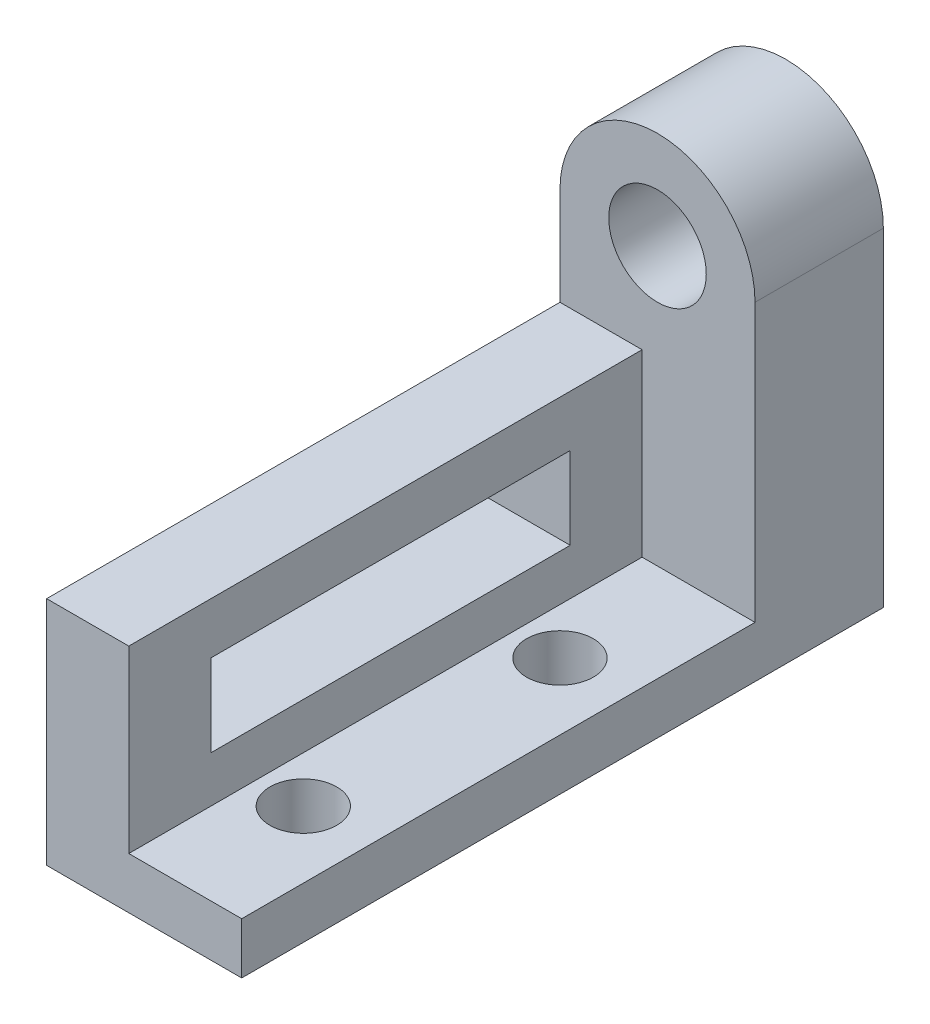
SolidWorks part; units mm, degrees
ref_plane "Front Plane" through (0, 0, 0) normal (0, 0, 1) x (1, 0, 0)
ref_plane "Top Plane" through (0, 0, 0) normal (0, 1, 0) x (1, 0, 0)
ref_plane "Right Plane" through (0, 0, 0) normal (1, 0, 0) x (0, 0, -1)
sketch "Sketch1" plane through (0, 0, 0) normal (1, 0, 0) x (0, 0, -1)
  line L0 (0, 10) -> (100, 10)
  line L1 (0, 0) -> (125, 0)
  line L2 (0, 0) -> (0, 10)
  line L3 (100, 83) -> (125, 83)
  line L4 (125, 0) -> (125, 83)
  line L5 (100, 10) -> (100, 83)
  line L6 (0, 10) -> (0, 45)
  line L7 (0, 45) -> (100, 45)
  line L9 (16, 35) -> (86, 35)
  line L10 (16, 35) -> (16, 19)
  line L11 (16, 19) -> (86, 19)
  line L12 (86, 35) -> (86, 19)
  dimension "D1" = 125
  dimension "D2" = 83
  dimension "D3" = 100
  dimension "D4" = 45
  dimension "D5" = 10
  dimension "D6" = 16
  dimension "D7" = 70
  dimension "D8" = 10
  dimension "D9" = 16
extrude "Boss-Extrude1" add sketch "Sketch1" along normal blind 38 contours L5 L0 L2 L1 L4 L3 region at (0, 8.4995, -50)
extrude "Boss-Extrude2" add sketch "Sketch1<3>" along normal blind 16 contours L7 L6 L0 L5 L9 L12 L11 L10 region at (0, 27.5, -1.0595)
sketch "Sketch1<3>" plane through (0, 0, 0) normal (1, 0, 0) x (0, 0, -1) same geometry as "Sketch1"
fillet "Fillet1" 2 edges at (38, 83, -112.5) (0, 83, -112.5) type full round first side face at (38, 31, -75) second side face at (0, 42.6667, -75) middle face at (19, 83, -112.5)
hole_wizard "Ø19.0 (19) Diameter Hole1" positions "3DSketch1" profile "Sketch2" hole size "Ø19.0" standard "ANSI Metric" end condition through all
sketch3d "3DSketch1"
  line L0 (19, 64, -100) -> (19, 64, -125) construction
  point P0 (19, 64, -100)
sketch "Sketch2" plane through (19, 64, -100) normal (1, 0, 0) x (0, -1, 0)
  line L0 (0, 0) -> (0, 25)
  line L1 (0, 25) -> (9.5, 25)
  line L2 (9.5, 25) -> (9.5, 0)
  line L5 (9.5, 0) -> (0, 0)
  line L11 (0, -6.35) -> (0, 107.95) construction
  dimension "Thru Hole Dia." = 19
  dimension "Thru Hole Depth" = 25
hole_wizard "Ø13.0 (13) Diameter Hole1" positions "3DSketch2" profile "Sketch3" hole size "Ø13.0" standard "ANSI Metric" end condition through all
sketch3d "3DSketch2"
  line L0 (38, 10, 0) -> (16, 10, 0) construction
  line L1 (38, 10, 0) -> (38, 10, -100) construction
  point P0 (25, 10, -25)
  point P2 (25, 10, -75)
  dimension "D1" = 25
  dimension "D2" = 50
  dimension "D3" = 13
sketch "Sketch3" plane through (25, 10, -25) normal (1, 0, 0) x (0, 0, 1)
  line L0 (0, 0) -> (0, 10)
  line L1 (0, 10) -> (6.5, 10)
  line L2 (6.5, 10) -> (6.5, 0)
  line L5 (6.5, 0) -> (0, 0)
  line L11 (0, -6.35) -> (0, 107.95) construction
  dimension "Thru Hole Dia." = 13
  dimension "Thru Hole Depth" = 10
